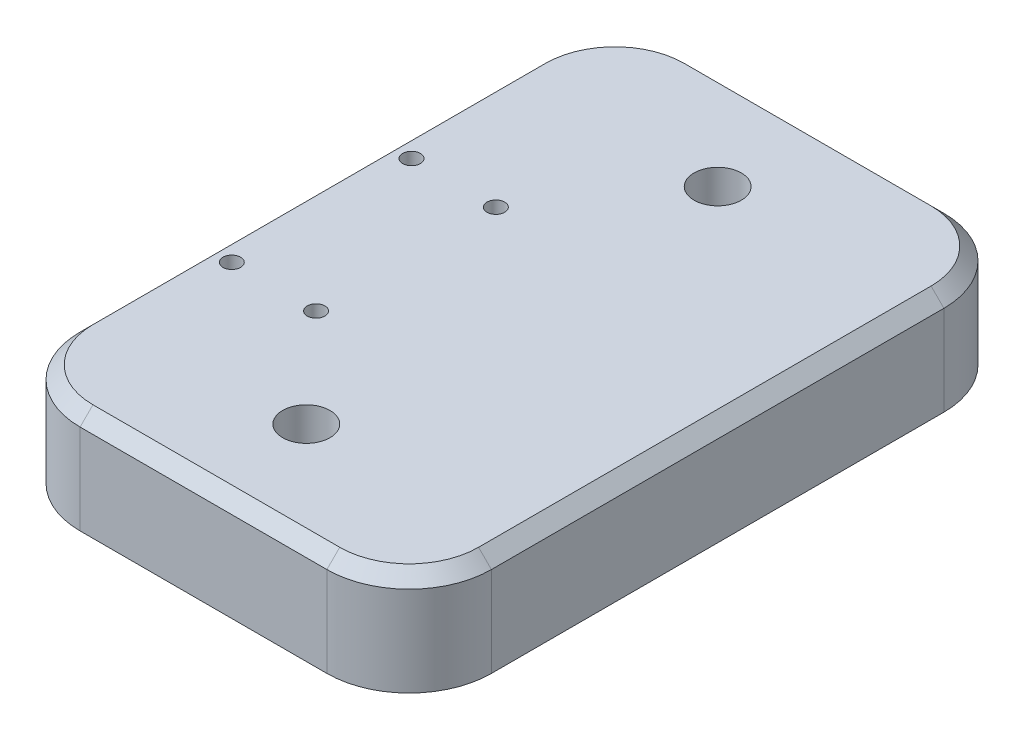
SolidWorks part; units mm, degrees
ref_plane "Front Plane" through (0, 0, 0) normal (0, 0, 1) x (1, 0, 0)
ref_plane "Top Plane" through (0, 0, 0) normal (0, 1, 0) x (1, 0, 0)
ref_plane "Right Plane" through (0, 0, 0) normal (1, 0, 0) x (0, 0, -1)
sketch "Sketch1" plane through (0, 0, 0) normal (1, 0, 0) x (0, 0, -1)
  line L3 (0, 12.7) -> (76.2, 12.7)
  line L4 (76.2, 12.7) -> (76.2, 0)
  line L5 (76.2, 0) -> (0, 0)
  line L6 (0, 12.7) -> (0, 0)
  dimension "D1" = 12.7
  dimension "D3" = 76.2
extrude "Boss-Extrude1" add sketch "Sketch1" along normal blind 50.8
sketch "Sketch3" plane through (0, 0, 0) normal (0, -1, 0) x (1, 0, 0)
  line L0 (50.8, 0) -> (0, 0) construction
  line L1 (25.4, -76.2) -> (25.4, 0) construction
  line L2 (50.8, -76.2) -> (0, -76.2) construction
  line L4 (0, -76.2) -> (0, 0) construction
  line L5 (50.8, -76.2) -> (0, -76.2) construction
  circle A1 centre (13.9065, -25.4) radius 1.0922
  circle A3 centre (25.4, -63.5) radius 2.921
  circle A4 centre (25.4, -12.7) radius 2.921
  circle A5 centre (3.4925, -25.4) radius 1.0922
  circle A6 centre (3.4925, -47.5996) radius 1.0922
  circle A7 centre (13.9065, -47.5996) radius 1.0922
  dimension "D1" = 2.1844
  dimension "D6" = 5.842
  dimension "D2" = 3.4925
  dimension "D3" = 22.1996
  dimension "D4" = 25.4
  dimension "D5" = 10.414
  dimension "D7" = 50.8
  dimension "D8" = 12.7
extrude "Cut-Extrude2" cut sketch "Sketch3" against normal through all
fillet "Fillet1" radius 10.16 4 edges at (0, 6.35, 0) (50.8, 6.35, 0) (0, 6.35, -76.2) (50.8, 6.35, -76.2)
chamfer "Chamfer1" distance 1.5875 angle 45 8 edges at (0, 12.7, -38.1) (2.9758, 12.7, -2.9758) (25.4, 12.7, 0) (47.8242, 12.7, -2.9758) (50.8, 12.7, -38.1) (47.8242, 12.7, -73.2242) (25.4, 12.7, -76.2) (2.9758, 12.7, -73.2242)
